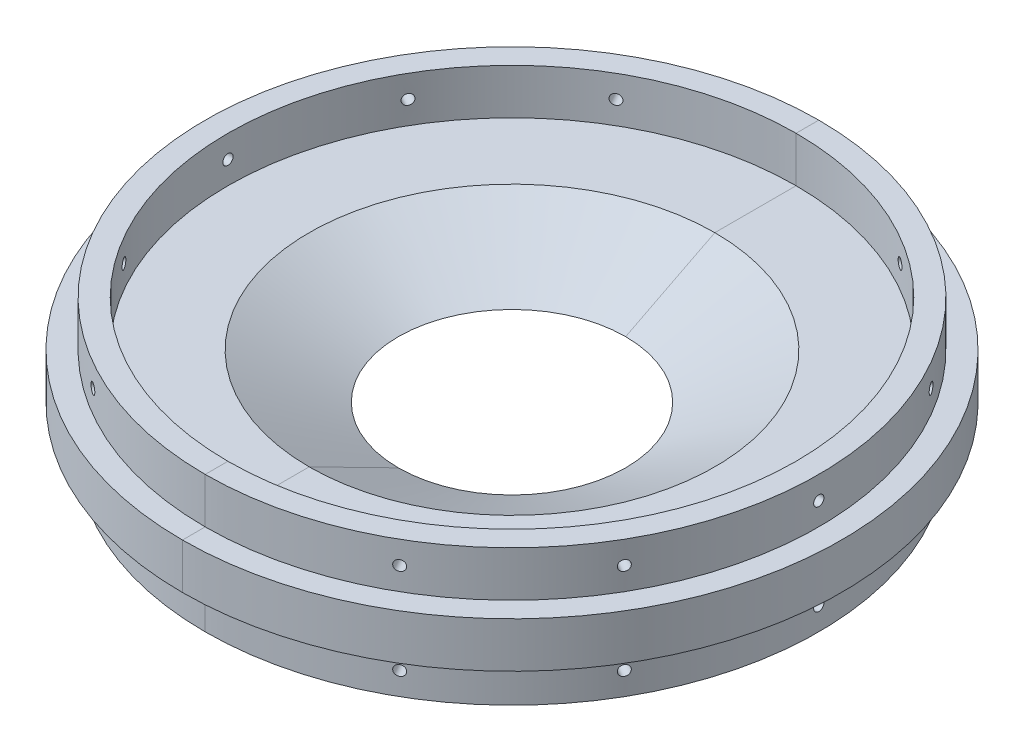
SolidWorks part; units mm, degrees
ref_plane "Front Plane" through (0, 0, 0) normal (0, 0, 1) x (1, 0, 0)
ref_plane "Top Plane" through (0, 0, 0) normal (0, 1, 0) x (1, 0, 0)
ref_plane "Right Plane" through (0, 0, 0) normal (1, 0, 0) x (0, 0, -1)
sketch "Sketch1" plane through (0, 0, 0) normal (0, 1, 0) x (1, 0, 0)
  circle A0 centre (0, 0) radius 92.075
  circle A1 centre (0, 0) radius 31.75
  dimension "D1" = 184.15
  dimension "D2" = 63.5
extrude "Boss-Extrude1" add sketch "Sketch1" along normal mid plane 12.7
sketch "Sketch5" plane through (0, 6.35, 0) normal (0, 1, 0) x (1, 0, 0)
  circle A0 centre (0, 0) radius 85.725
  circle A1 centre (0, 0) radius 79.375
  dimension "D1" = 171.45
  dimension "D2" = 158.75
extrude "Boss-Extrude2" add sketch "Sketch5" along normal blind 12.7
ref_plane "Plane1" through (0, 0, -85.725) normal (0, 0, -1) x (-1, 0, 0)
sketch "Sketch6" plane through (0, 0, -85.725) normal (0, 0, -1) x (-1, 0, 0)
  line L0 (0, 55) -> (0, -55) construction
  line L1 (92.075, 6.35) -> (-92.075, 6.35) construction
  circle A0 centre (0, 12.7) radius 1.4351
  dimension "D1" = 2.8702
  dimension "D2" = 6.35
extrude "Cut-Extrude1" cut sketch "Sketch6" against normal blind 12.7
pattern_circular "CirPattern1" count 12 over 360 about axis through (0, 6.35, 0) along (0, -1, 0) of "Cut-Extrude1" reverse direction yes
mirror "Mirror1" about plane through (0, 0, 0) normal (0, 1, 0) of "CirPattern1", "Cut-Extrude1", "Boss-Extrude2"
sketch "Sketch7" plane through (0, 19.05, 0) normal (0, 1, 0) x (1, 0, 0)
  line L0 (-25.7878, 75.0692) -> (-28.1663, 80.9657)
  line L1 (28.1663, 80.9657) -> (25.7878, 75.0692)
  arc A0 (28.1663, 80.9657) -> (-28.1663, 80.9657) centre (0, 0) ccw
  circle A1 centre (0, 0) radius 85.725 construction
  arc A2 (25.7878, 75.0692) -> (-25.7878, 75.0692) centre (0, 0) ccw
  circle A3 centre (0, 0) radius 79.375 construction
extrude "Boss-Extrude3" add sketch "Sketch7" against normal up to surface (12.7 mm away) up to face at (0, 6.35, 85.725)
mirror "Mirror3" about plane through (0, 0, 0) normal (0, 1, 0) of "Boss-Extrude3"
mirror "Mirror4" about plane through (0, 0, 0) normal (0, 0, 1) of "Boss-Extrude3"
mirror "Mirror5" about plane through (0, 0, 0) normal (0, 1, 0) of "Mirror4"
sketch "Sketch4" plane through (0, 0, 0) normal (0, 0, 1) x (1, 0, 0)
  line L0 (0, 23.2786) -> (0, -14.9525) construction
sketch "Sketch3" plane through (0, 0, 0) normal (0, 0, 1) x (1, 0, 0)
  line L0 (-31.75, -6.35) -> (-56.6752, 6.35)
  line L1 (92.075, 6.35) -> (-92.075, 6.35) construction
  line L2 (-56.6752, 6.35) -> (-31.75, 6.35)
  line L3 (-31.75, 6.35) -> (-31.75, -6.35)
  line L4 (-31.75, -6.35) -> (31.75, -6.35) construction
  line L5 (31.75, 6.35) -> (-31.75, 6.35) construction
  dimension "D1" = 27
revolve "Cut-Revolve1" cut sketch "Sketch3" angle 360 about L0
split "Split1" trim tools "Right Plane" bodies to split 103 resulting bodies 115 116
